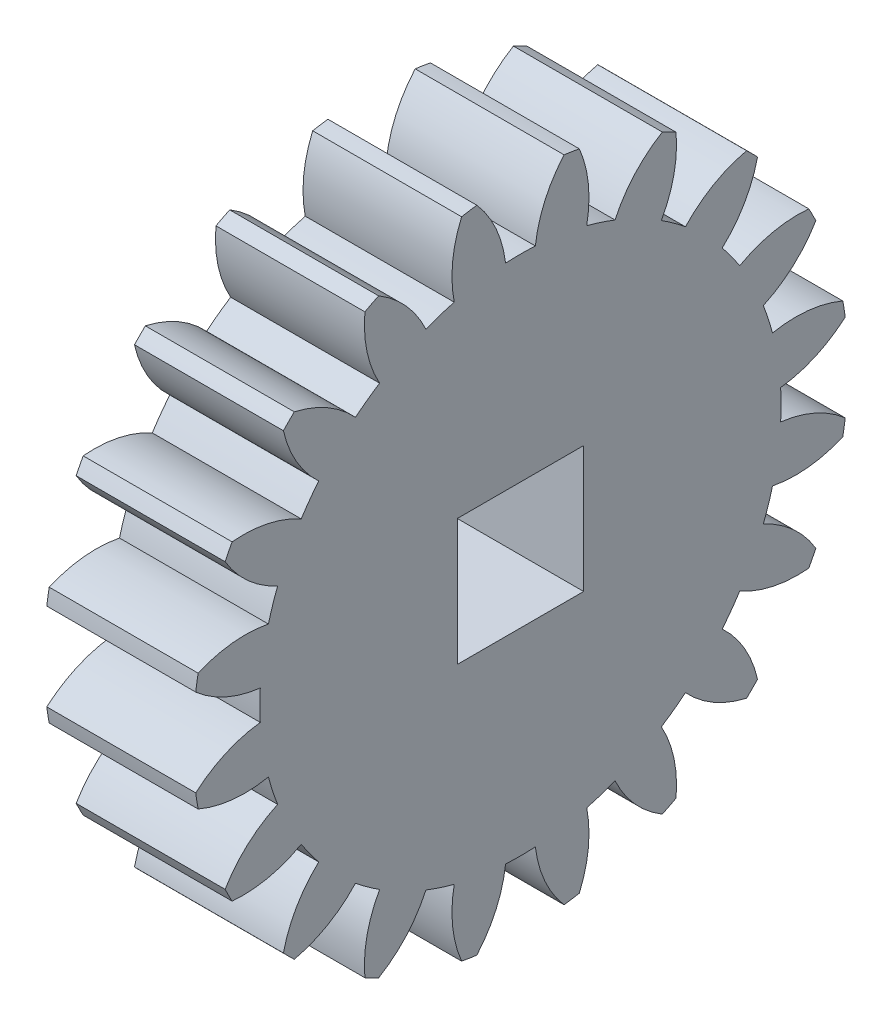
SolidWorks part; units mm, degrees
ref_plane "Plane1" through (0, 0, 0) normal (0, 0, 1) x (1, 0, 0)
ref_plane "Plane2" through (0, 0, 0) normal (0, 1, 0) x (1, 0, 0)
ref_plane "Plane3" through (0, 0, 0) normal (1, 0, 0) x (0, 0, -1)
other "Configuration Table"
sketch "HoldingSke" plane through (0, 0, 0) normal (0, 1, 0) x (1, 0, 0)
  line L0 (0, 0) -> (0.9397, -0.342)
  line L1 (-15, 0) -> (100, 0) construction
  line L2 (0, 0) -> (-2.1039, 2.3779)
  line L3 (0, 0) -> (-11.863, 4.5341)
  line L4 (0, 0) -> (8.1152, 2.9537)
  line L5 (0, 0) -> (-46.8476, -17.4728)
  line L6 (0, 0) -> (-4.1448, -2.7965)
  line L7 (-2.1039, 2.3779) -> (8.6586, 51.2059)
  line L8 (-76.2, 54.61) -> (-76.1, 54.61)
  line L9 (-71.009, 38.7566) -> (-53.1078, 45.2721)
  line L10 (-76.2, 71.12) -> (104.1128, 71.12)
  line L11 (0, 0) -> (-5, 0)
  line L12 (-76.2, 101.6) -> (-76.162, 101.6)
  line L13 (24.9733, 27.94) -> (52.9518, 28.4284)
  line L14 (24.9733, 27.94) -> (24.9743, 27.94)
  line L15 (24.9733, 27.94) -> (100.4006, 29.5858)
  line L16 (-63.627, -1) -> (-12.827, -1)
  circle A0 centre (0, 0) radius 0.4
  circle A1 centre (0, 0) radius 8.749
  circle A2 centre (0, 0) radius 37.5
  circle A3 centre (0, 0) radius 0.4
  dimension "Hub_dia" = 75
  dimension "Bore" = 0.8
  dimension "MBD" = 0.8
  dimension "Pitch" = 1
  dimension "Overall_len" = 50
  dimension "Thickness" = 5
  dimension "OAL" = 50.0001
  dimension "T_dim" = 0.1
  dimension "Ap" = 20
  dimension "H" = 19.05
  dimension "Pitch_radius" = 180.3128
  dimension "Width" = 5
  dimension "Backlash" = 0.038
  dimension "Addendum_fac" = 1
  dimension "Dedendum_fac" = 1.25
  dimension "Clearance_fac" = 0.25
  dimension "Dedendum_add" = 0.001
  dimension "Module" = 1
sketch "BasProSke" plane through (0, 0, 0) normal (0, 1, 0) x (1, 0, 0)
  line L0 (-10, 0) -> (60, 0) construction
  line L1 (0, 0) -> (0, 11)
  line L2 (0, 0) -> (5, 0)
  line L3 (5, 0) -> (5, 11)
  line L4 (5, 11) -> (0, 11)
  dimension "Thickness" = 5
revolve "Base-Revolve" add sketch "BasProSke" angle 360 about L0
sketch "TooCutSke" plane through (0, 0, 0) normal (1, 0, 0) x (0, 0, -1)
  line L1 (0, 0) -> (0, 107) construction
  line L2 (0, 0) -> (-0.8511, 9.9637) construction
  line L3 (0, 0) -> (-3.1206, 19.7028) construction
  line L4 (-0.8511, 9.9637) -> (-1.5603, 9.8514) construction
  arc A0 (0.4999, 8.7347) -> (-0.4999, 8.7347) centre (0, 0) ccw
  arc A1 (1.4852, 10.9249) -> (-1.4852, 10.9249) centre (0, 0) ccw
  circle A2 centre (0, 0) radius 10 construction
  circle A3 centre (0, 0) radius 9.3969 construction
  arc A4 (-0.4999, 8.7347) -> (-1.4852, 10.9249) centre (-4.4722, 8.2645) ccw
  arc A5 (1.4852, 10.9249) -> (0.4999, 8.7347) centre (4.4722, 8.2645) ccw
extrude "ToothCut" cut sketch "TooCutSke" along normal through all
fillet "Breaks" [suppressed] radius 0.02 tangent propagation no
fillet "RootFillets" [suppressed] radius 0.251
pattern_circular "TeethCuts" count 20 every 18 about axis through (-10, 0, 0) along (1, 0, 0) of "ToothCut", "RootFillets", "Breaks"
sketch "HubNeaOneSke" plane through (0, 0, 0) normal (-1, 0, 0) x (0, 0, 1)
  circle A0 centre (0, 0) radius 8.749
extrude "HubNearOne" [suppressed] add sketch "HubNeaOneSke" along normal blind 45.0001
sketch "HubNeaBotSke" plane through (0, 0, 0) normal (-1, 0, 0) x (0, 0, 1)
  circle A0 centre (0, 0) radius 8.749
extrude "HubNearBoth" [suppressed] add sketch "HubNeaBotSke" along normal blind 22.5
ref_plane "FarPln" through (5, 0, 0) normal (1, 0, 0) x (0, 0, -1)
sketch "HubFarSke" plane through (5, 0, 0) normal (1, 0, 0) x (0, 0, -1)
  circle A0 centre (0, 0) radius 8.749
extrude "HubFar" [suppressed] add sketch "HubFarSke" along normal blind 22.5
sketch "BorSke" plane through (0, 0, 0) normal (1, 0, 0) x (0, 0, -1)
  circle A0 centre (0, 0) radius 0.4
  dimension "Diameter" = 0.8
extrude "Bore" cut sketch "BorSke" along normal mid plane 100.0001
sketch "KeySke" plane through (0, 0, 0) normal (1, 0, 0) x (0, 0, -1)
  line L0 (-0.05, 0) -> (-0.05, 0.5)
  line L1 (-0.05, 0.5) -> (0.05, 0.5)
  line L2 (0.05, 0.5) -> (0.05, 0)
  line L3 (0, 0) -> (0, 34) construction
  line L4 (-0.05, 0) -> (0.05, 0)
  dimension "Offset" = 0.5
  dimension "Width" = 0.1
extrude "Keyway" [suppressed] cut sketch "KeySke" along normal mid plane 100.0001
pattern_circular "Keyway2" [suppressed] count 2 every 90 about axis through (-10, 0, 0) along (1, 0, 0)
sketch "Sketch1" plane through (5, 0, 0) normal (1, 0, 0) x (0, 0, -1)
  line L1 (-2.1213, -2.1213) -> (2.1213, -2.1213)
  line L2 (-2.1213, -2.1213) -> (-2.1213, 2.1213)
  line L3 (-2.1213, 2.1213) -> (2.1213, 2.1213)
  line L4 (2.1213, -2.1213) -> (2.1213, 2.1213)
  circle A0 centre (0, 0) radius 3 construction
  dimension "D1" = 6
extrude "Cut-Extrude1" cut sketch "Sketch1" against normal through all
equation "' \"Module@HoldingSke\" = 6.35"
equation "' \"Num_teeth@HoldingSke\" = 12"
equation "' \"Ap@HoldingSke\" =  20"
equation "' \"Ap@HoldingSke\" = 20"
equation "' \"Width@HoldingSke\" = 0.5 * 25.4"
equation "' \"Hub_dia@HoldingSke\"= 1 * 25.4"
equation "' \"Hub_dia@HoldingSke\" = 1 * 25.4"
equation "' \"Overall_len@HoldingSke\" = 1.0 * 25.4"
equation "' \"Bore@HoldingSke\" = 0.75 * 25.4"
equation "' \"T_dim@HoldingSke\" = 0.1 * 25.4"
equation "' \"Width@KeySke\" = 0.25 * 25.4"
equation "' \"Show_teeth@HoldingSke\" = 13"
equation "' \"Backlash@HoldingSke\" = 0.009 * 25.4"
equation "' \"Addendum_fac@HoldingSke\" = 1.0"
equation "' \"Dedendum_fac@HoldingSke\" = 1.25"
equation "' \"Dedendum_add@HoldingSke\" = 0.00005 * 25.4"
equation "' \"Clearance_fac@HoldingSke\" = 0.25"
equation "\"Pitch@HoldingSke\" = 1 / \"Module@HoldingSke\""
equation "\"Overcut_dia@TooCutSke\" = (\"Num_teeth@HoldingSke\" + 2 * \"Addendum_fac@HoldingSke\") / \"Pitch@HoldingSke\" + 0.002 * 25.4"
equation "\"Pitch_dia@TooCutSke\" = \"Num_teeth@HoldingSke\" / \"Pitch@HoldingSke\""
equation "\"Base_dia@TooCutSke\" = \"Num_teeth@HoldingSke\" / \"Pitch@HoldingSke\" * cos((\"Ap@HoldingSke\"  * 3.14159265 / 180))"
equation "\"Root_dia@TooCutSke\" = (\"Num_teeth@HoldingSke\" + 2) / \"Pitch@HoldingSke\" - 2 * (\"Addendum_fac@HoldingSke\" + \"Dedendum_fac@HoldingSke\") / \"Pitch@HoldingSke\" - \"Dedendum_add@HoldingSke\" * 2"
equation "\"Half_ang@TooCutSke\" = 180 / \"Num_teeth@HoldingSke\""
equation "\"Half_CT@TooCutSke\" = \"Num_teeth@HoldingSke\" / \"Pitch@HoldingSke\" * sin((3.14159265 / 2 / \"Num_teeth@HoldingSke\")) / 2 - 7 * \"Backlash@HoldingSke\" / 4"
equation "\"Flank_rad@TooCutSke\" = \"Num_teeth@HoldingSke\" / \"Pitch@HoldingSke\" / 5"
equation "\"Radius@RootFillets\" = \"Clearance_fac@HoldingSke\" / \"Pitch@HoldingSke\" + \"Dedendum_add@HoldingSke\""
equation "\"Break_rad@Breaks\" = 0.02 / \"Pitch@HoldingSke\""
equation "\"Thickness@HoldingSke\" = \"Width@HoldingSke\""
equation "\"OAL@HoldingSke\" = \"Thickness@HoldingSke\""
equation "\"MHD@HoldingSke\" = (\"Num_teeth@HoldingSke\" + 2) / \"Pitch@HoldingSke\" - 2 * (\"Addendum_fac@HoldingSke\" + \"Dedendum_fac@HoldingSke\")  / \"Pitch@HoldingSke\" - \"Dedendum_add@HoldingSke\" * 2"
equation "\"MBD@HoldingSke\" = (\"Num_teeth@HoldingSke\" + 2) / \"Pitch@HoldingSke\" - 2 * (\"Addendum_fac@HoldingSke\" + \"Dedendum_fac@HoldingSke\")  / \"Pitch@HoldingSke\" - \"Dedendum_add@HoldingSke\" * 2 - 0.002 * 25.4"
equation "\"MHD@HoldingSke\" = ((sgn( \"MHD@HoldingSke\" - \"Hub_dia@HoldingSke\" )-1)*( \"MHD@HoldingSke\" - \"Hub_dia@HoldingSke\" ))/-2+ \"Hub_dia@HoldingSke\""
equation "\"MBD@HoldingSke\" = ((sgn( \"MBD@HoldingSke\" - \"Bore@HoldingSke\" )-1)*( \"MBD@HoldingSke\" - \"Bore@HoldingSke\" ))/-2+ \"Bore@HoldingSke\""
equation "\"OAL@HoldingSke\" = ((sgn( \"OAL@HoldingSke\" - \"Overall_len@HoldingSke\" )+1)*( \"OAL@HoldingSke\" - \"Overall_len@HoldingSke\" ))/2 + \"Overall_len@HoldingSke\" + 0.000002 * 25.4"
equation "\"Num_teeth@TeethCuts\" = int( \"Show_teeth@HoldingSke\" ) + 1"
equation "\"Num_teeth@TeethCuts\" = ((sgn( \"Num_teeth@TeethCuts\" - \"Num_teeth@HoldingSke\" )-1)*( \"Num_teeth@TeethCuts\" - \"Num_teeth@HoldingSke\" ))/-2+ \"Num_teeth@HoldingSke\""
equation "\"Num_teeth@TeethCuts\" = ((sgn( \"Num_teeth@TeethCuts\" - 2.0)+1)*( \"Num_teeth@TeethCuts\" - 2.0))/2 +2.0"
equation "\"Angle@TeethCuts\" = 360.0 / \"Num_teeth@HoldingSke\""
equation "\"Diameter@BasProSke\" = (\"Num_teeth@HoldingSke\" + 2 * \"Addendum_fac@HoldingSke\") / \"Pitch@HoldingSke\""
equation "\"Thickness@BasProSke\"  = \"Thickness@HoldingSke\""
equation "' \"Fillet_rad@BasProSke\" =  \"Thickness@HoldingSke\" * 0.05"
equation "' \"Fillet_rad@BasProSke\" = \"Thickness@HoldingSke\" * 0.05"
equation "\"MHD@HoldingSke\" = ((sgn( \"MHD@HoldingSke\" - \"Root_dia@TooCutSke\" )-1)*( \"MHD@HoldingSke\" - \"Root_dia@TooCutSke\" ))/-2+ \"Root_dia@TooCutSke\""
equation "\"Diameter@HubNeaOneSke\" = \"MHD@HoldingSke\""
equation "\"Length@HubNearOne\" = \"OAL@HoldingSke\" - \"Thickness@BasProSke\""
equation "\"Diameter@HubNeaBotSke\" = \"MHD@HoldingSke\""
equation "\"Length@HubNearBoth\" = ( \"OAL@HoldingSke\" - \"Thickness@BasProSke\" ) / 2.0"
equation "\"Thickness@FarPln\" = \"Thickness@BasProSke\""
equation "\"Diameter@HubFarSke\" = \"MHD@HoldingSke\""
equation "\"Length@HubFar\" = ( \"OAL@HoldingSke\" - \"Thickness@BasProSke\" ) / 2.0"
equation "\"Diameter@BorSke\" = \"MBD@HoldingSke\""
equation "\"D1@Bore\" = \"OAL@HoldingSke\" * 2.0"
equation "\"D1@Keyway\" = \"OAL@HoldingSke\" * 2.0"
equation "\"Offset@KeySke\" = \"T_dim@HoldingSke\" + \"MBD@HoldingSke\" / 2.0"
